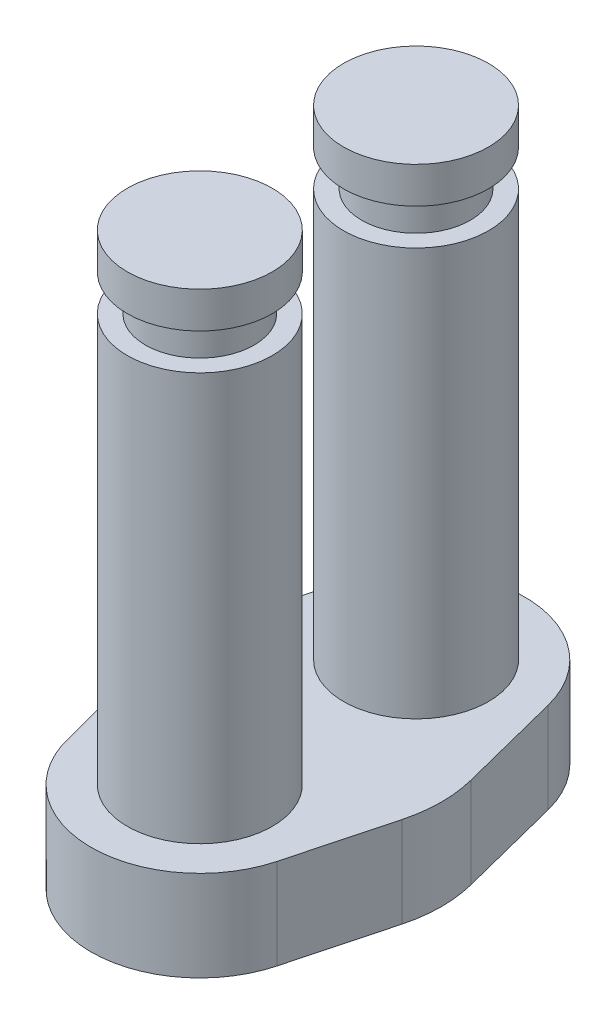
SolidWorks part; units mm, degrees
ref_plane "Front Plane" through (0, 0, 0) normal (0, 0, 1) x (1, 0, 0)
ref_plane "Top Plane" through (0, 0, 0) normal (0, 1, 0) x (1, 0, 0)
ref_plane "Right Plane" through (0, 0, 0) normal (1, 0, 0) x (0, 0, -1)
sketch "Sketch2" plane through (0, 0, 0) normal (0, 1, 0) x (1, 0, 0)
  line L0 (3.75, 7.5) -> (3.75, -7.5) construction
  line L1 (-3.4934, -1.9449) -> (-1.9217, -7.7985)
  line L2 (10.9985, -1.9261) -> (9.5488, -7.3818)
  line L3 (11.0189, 1.8474) -> (9.5651, 7.5676)
  line L4 (-2.0651, 7.5676) -> (-3.5189, 1.8474)
  circle A0 centre (7.5, 0) radius 2.5 construction
  circle A1 centre (0, 0) radius 2.5 construction
  circle A2 centre (3.75, 0) radius 7.5
  circle A3 centre (3.75, 6.0897) radius 4 construction
  circle A4 centre (3.75, -5.841) radius 4 construction
  circle A5 centre (3.75, 6.0897) radius 6
  circle A6 centre (3.75, -5.841) radius 6
  dimension "D1" = 7.5
  dimension "D2" = 5
  dimension "D4" = 15
  dimension "D5" = 12
  dimension "D6" = 12
  dimension "D7" = 8
  dimension "D8" = 8
  dimension "D3" = 3.75
extrude "Boss-Extrude2" add sketch "Sketch2" along normal blind 5 contours A2 A6 A0 A5 A1 | A6 A2 L1 | A6 A2 A5 A0 | A6 L2 A2 | A6 A1 A5 A2 | A6 A2 L1 | A6 A0 A5 | A5 A6 | A6 A5 A1 | A6 A5 A0 A2 A1 | A2 A5 | A5 A2 L3 | A5 L4 A2 region at (-2.5745, 0, 4.6608) region at (-1.6671, 0, -0.0703) region at (3.751, 0, 8.7182) region at (-2.5748, 0, -4.7398) region at (3.75, 0, 3.7712) region at (3.75, 0, -8.8393) region at (3.75, 0, -3.8922) region at (9.1671, 0, -0.0703) region at (10.0744, 0, 4.6847) region at (3.75, 0, -0.1244) region at (10.0748, 0, -4.7398)
sketch "Sketch3" plane through (0, 5, 0) normal (0, 1, 0) x (1, 0, 0)
  line L0 (3.75, -11.841) -> (3.75, 12.0897) construction
  line L1 (-3.7498, -0.0504) -> (11.2499, -0.0406) construction
  circle A0 centre (3.75, -5.841) radius 4
  circle A1 centre (3.75, 6.0897) radius 4
  arc A2 (-1.9217, -7.7985) -> (9.5488, -7.3818) centre (3.75, -5.841) ccw construction
  arc A3 (9.5651, 7.5676) -> (-2.0651, 7.5676) centre (3.75, 6.0897) ccw construction
  arc A4 (-3.5189, 1.8474) -> (-3.4934, -1.9449) centre (3.75, 0) ccw construction
  arc A5 (10.9985, -1.9261) -> (11.0189, 1.8474) centre (3.75, 0) ccw construction
  dimension "D1" = 8
extrude "Boss-Extrude3" add sketch "Sketch3" along normal blind 22.5
sketch "Sketch4" plane through (0, 27.5, 0) normal (0, 1, 0) x (1, 0, 0)
  circle A0 centre (3.75, -5.841) radius 3
  circle A1 centre (3.75, 6.0897) radius 3
  circle A2 centre (3.75, -5.841) radius 4 construction
  circle A3 centre (3.75, 6.0897) radius 4 construction
  dimension "D1" = 6
  dimension "D2" = 6
extrude "Boss-Extrude4" add sketch "Sketch4" along normal blind 2
sketch "Sketch5" plane through (0, 29.5, 0) normal (0, 1, 0) x (1, 0, 0)
  circle A0 centre (3.75, -5.841) radius 4
  circle A1 centre (3.75, 6.0897) radius 4
  dimension "D1" = 8
  dimension "D2" = 8
extrude "Boss-Extrude5" add sketch "Sketch5" along normal blind 2
hole_wizard "#6 Clearance Hole1" positions "Sketch6" profile "Sketch7" hole size "#6" standard "ANSI Inch" end condition through all
sketch "Sketch6" plane through (0, 5, 0) normal (0, 1, 0) x (1, 0, 0)
  point P7 (3.75, 6.0897)
  point P10 (3.75, -5.841)
sketch "Sketch7" plane through (3.75, 5, -6.0897) normal (1, 0, 0) x (0, 0, 1)
  line L0 (0, 0) -> (0, 5)
  line L1 (0, 5) -> (1.8986, 5)
  line L2 (1.8986, 5) -> (1.8986, 0)
  line L5 (1.8986, 0) -> (0, 0)
  line L11 (0, -6.35) -> (0, 107.95) construction
  dimension "Thru Hole Dia." = 3.7973
  dimension "Thru Hole Depth" = 5
